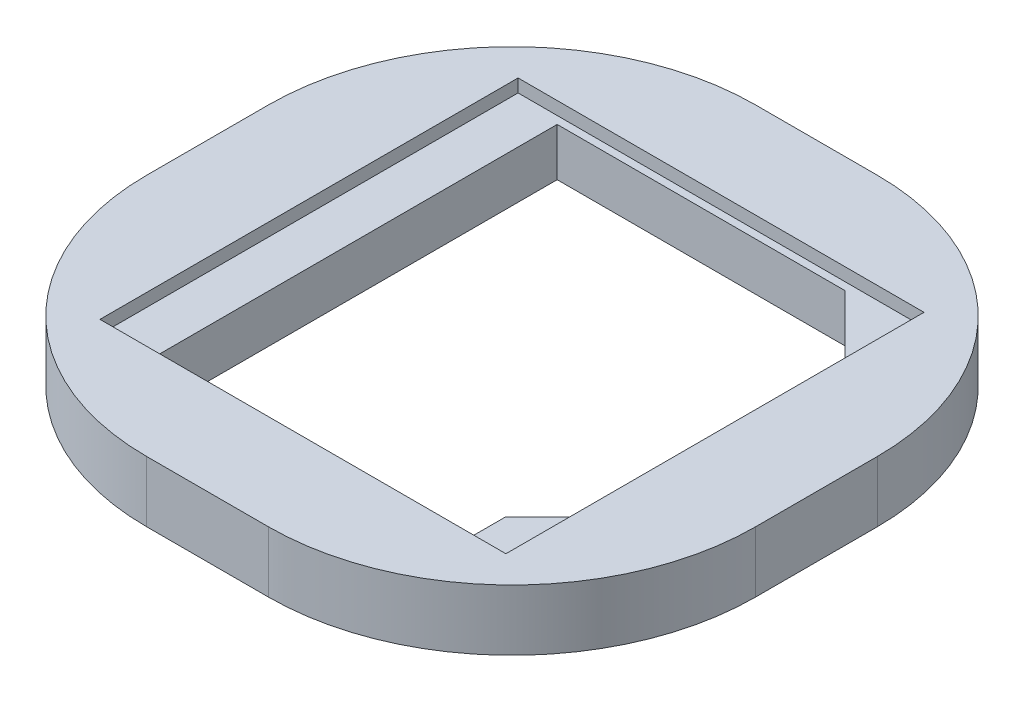
SolidWorks part; units mm, degrees
ref_plane "Front Plane" through (0, 0, 0) normal (0, 0, 1) x (1, 0, 0)
ref_plane "Top Plane" through (0, 0, 0) normal (0, 1, 0) x (1, 0, 0)
ref_plane "Right Plane" through (0, 0, 0) normal (1, 0, 0) x (0, 0, -1)
sketch "Sketch2" plane through (0, 0, 0) normal (0, 1, 0) x (1, 0, 0)
  line L1 (-37.5, -37.5) -> (37.5, -37.5)
  line L2 (-37.5, -37.5) -> (-37.5, 37.5)
  line L3 (-37.5, 37.5) -> (37.5, 37.5)
  line L4 (37.5, -37.5) -> (37.5, 37.5)
  line L5 (-37.5, -37.5) -> (37.5, 37.5) construction
  line L6 (-37.5, 37.5) -> (37.5, -37.5) construction
  point P0 (0, 0)
  dimension "D1" = 75
  dimension "D2" = 75
extrude "Base" add sketch "Sketch2" along normal blind 7.5
sketch "Sketch3" plane through (0, 7.5, 0) normal (0, 1, 0) x (1, 0, 0)
  line L1 (-25, -25.75) -> (25, -25.75)
  line L2 (-25, -25.75) -> (-25, 25.75)
  line L3 (-25, 25.75) -> (25, 25.75)
  line L4 (25, -25.75) -> (25, 25.75)
  line L5 (-25, -25.75) -> (25, 25.75) construction
  line L6 (-25, 25.75) -> (25, -25.75) construction
  point P0 (0, 0)
  dimension "D1" = 50
  dimension "D2" = 51.5
extrude "Slot" cut sketch "Sketch3" against normal blind 1.6
sketch "Sketch4" plane through (0, 5.9, 0) normal (0, 1, 0) x (1, 0, 0)
  line L0 (-19.238, -25.75) -> (-19.238, 24.8007)
  line L1 (-19.238, 24.8007) -> (16.1992, 24.8007)
  line L3 (16.1992, 24.8007) -> (25, 16)
  line L5 (25, 16) -> (25, -14.6954)
  line L6 (25, -25.75) -> (25, 25.75) construction
  line L7 (25, -14.6954) -> (19.45, -20.2454)
  line L8 (19.45, -20.2454) -> (19.45, -25.75)
  line L9 (-25, -25.75) -> (25, -25.75) construction
  line L10 (19.45, -25.75) -> (-19.238, -25.75)
  line L11 (25, -25.75) -> (25, 25.75) construction
  point P2 (25, 16)
extrude "Cut-Extrude2" cut sketch "Sketch4" against normal up to surface (5.9 mm away) up to face at (0, 0, 0)
fillet "Fillet1" radius 30 4 edges at (37.5, 3.75, -37.5) (37.5, 3.75, 37.5) (-37.5, 3.75, 37.5) (-37.5, 3.75, -37.5)
